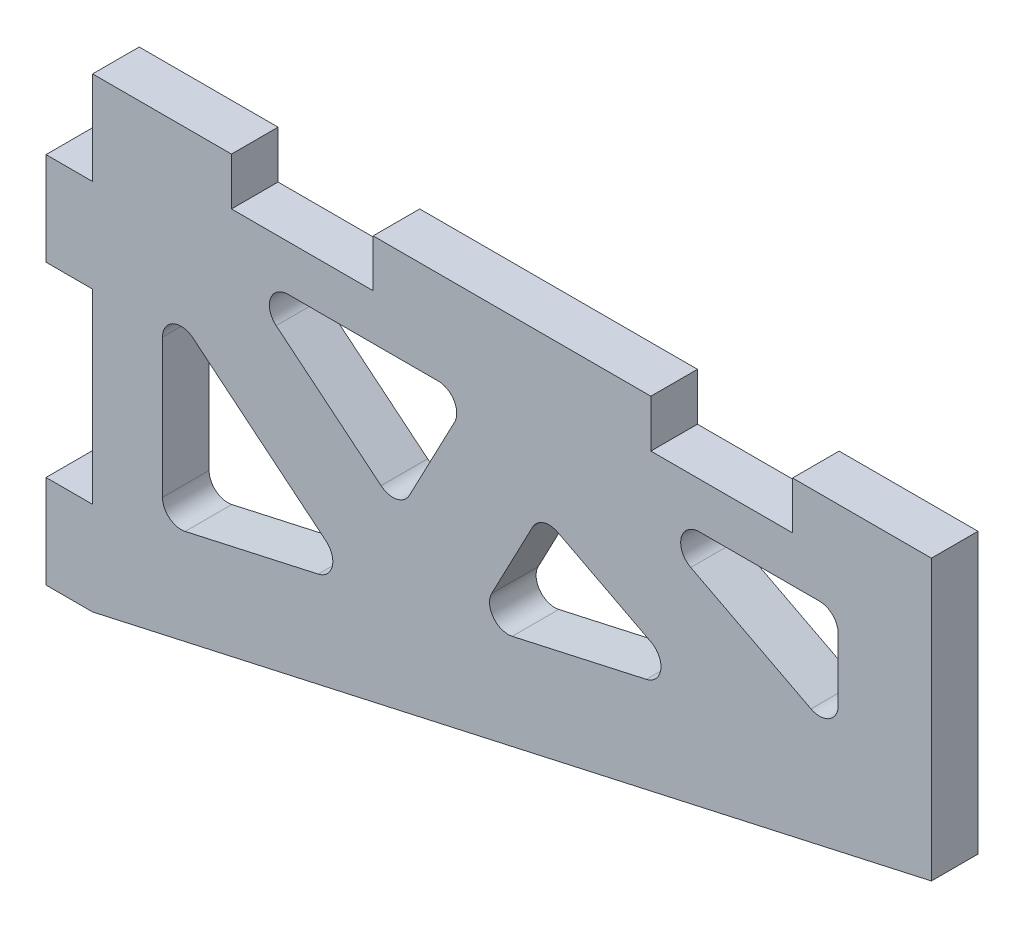
SolidWorks part; units mm, degrees
ref_plane "Front Plane" through (0, 0, 0) normal (0, 0, 1) x (1, 0, 0)
ref_plane "Top Plane" through (0, 0, 0) normal (0, 1, 0) x (1, 0, 0)
ref_plane "Right Plane" through (0, 0, 0) normal (1, 0, 0) x (0, 0, -1)
sketch "Sketch2" plane through (0, 0, 0) normal (0, 0, 1) x (1, 0, 0)
  line L0 (0, -127) -> (27.7435, -127)
  line L5 (0, -69.85) -> (40.1279, -69.85) construction
  line L6 (0, -127) -> (0, -69.85) construction
  line L7 (0, -63.5) -> (45.8652, -63.5) construction
  line L8 (0, -63.5) -> (114.3, -38.1)
  line L9 (114.3, -38.1) -> (114.3, 0)
  line L11 (0, 0) -> (0, -12.7) construction
  line L12 (19.05, 0) -> (19.05, -6.35) construction
  line L13 (0, -63.5) -> (0, -25.4) construction
  line L16 (-6.35, -63.5) -> (0, -63.5)
  line L18 (0, 0) -> (19.05, 0)
  line L20 (-6.35, -12.7) -> (0, -12.7)
  line L21 (0, -25.4) -> (0, -50.8)
  line L22 (0, -50.8) -> (-6.35, -50.8)
  line L23 (-6.35, -50.8) -> (-6.35, -63.5)
  line L24 (0, 0) -> (0, -12.7)
  line L25 (-6.35, -12.7) -> (-6.35, -25.4)
  line L26 (-6.35, -25.4) -> (0, -25.4)
  line L27 (0, -25.4) -> (0, -63.5) construction
  line L28 (0, -12.7) -> (0, 0) construction
  line L29 (-6.35, -63.5) -> (-6.35, 0) construction
  line L30 (19.05, -6.35) -> (38.1, -6.35) construction
  line L31 (38.1, -6.35) -> (38.1, 0) construction
  line L32 (18.923, 0) -> (18.923, -6.477)
  line L33 (18.923, -6.477) -> (38.227, -6.477)
  line L34 (38.227, -6.477) -> (38.227, 0)
  line L35 (57.15, 0) -> (57.15, -20.9685) construction
  line L36 (76.073, -6.477) -> (76.073, 0)
  line L37 (95.377, -6.477) -> (76.073, -6.477)
  line L38 (95.377, 0) -> (95.377, -6.477)
  line L39 (76.2, -6.35) -> (76.2, 0) construction
  line L40 (95.25, -6.35) -> (76.2, -6.35) construction
  line L41 (95.25, 0) -> (95.25, -6.35) construction
  line L42 (38.1, 0) -> (76.2, 0)
  line L43 (95.25, 0) -> (114.3, 0)
  point P21 (-6.35, -31.75)
  dimension "D1" = 57.15
  dimension "D2" = 6.35
  dimension "D3" = 114.3
  dimension "D4" = 12.7
  dimension "D5" = 12.7
  dimension "D6" = 6.35
  dimension "D7" = 38.1
  dimension "D8" = 12.7
  dimension "D9" = 6.35
  dimension "D10" = 19.05
  dimension "D11" = 19.05
  dimension "D13" = 19.05
  dimension "D12" = 0.127
extrude "Boss-Extrude1" add sketch "Sketch2" against normal blind 6.35 contours L22 L23 L16 L8 L9 L18 L20 L21 region at (50.6118, -27.2649, 0)
sketch "Sketch3" plane through (0, 0, 0) normal (0, 0, 1) x (1, 0, 0)
  line L0 (9.525, -12.7) -> (9.525, -48.3735)
  line L1 (9.525, -48.3735) -> (101.6, -27.9124)
  line L2 (101.6, -27.9124) -> (101.6, -12.7)
  line L3 (101.6, -12.7) -> (9.525, -12.7)
  line L4 (0, 0) -> (18.923, 0) construction
  line L5 (114.3, -38.1) -> (114.3, 0) construction
  line L6 (0, -63.5) -> (114.3, -38.1) construction
  line L7 (0, -25.4) -> (0, -50.8) construction
  line L8 (9.525, -12.7) -> (43.7122, -40.7764) construction
  line L9 (13.5551, -7.7928) -> (47.7422, -35.8692)
  line L10 (5.4949, -17.6072) -> (39.6821, -45.6836)
  line L11 (43.7122, -40.7764) -> (58.4566, -12.7) construction
  line L12 (38.0902, -37.824) -> (52.8347, -9.7476)
  line L13 (49.3341, -43.7288) -> (64.0785, -15.6524)
  line L14 (58.4566, -12.7) -> (98.6776, -33.55) construction
  line L17 (61.379, -7.0625) -> (101.6, -27.9124)
  line L18 (55.5342, -18.3375) -> (95.7552, -39.1875)
  arc A0 (13.5551, -7.7928) -> (5.4949, -17.6072) centre (9.525, -12.7) ccw
  arc A1 (39.6821, -45.6836) -> (47.7422, -35.8692) centre (43.7122, -40.7764) ccw
  arc A2 (38.0902, -37.824) -> (49.3341, -43.7288) centre (43.7122, -40.7764) ccw
  arc A3 (64.0785, -15.6524) -> (52.8347, -9.7476) centre (58.4566, -12.7) ccw
  arc A6 (61.379, -7.0625) -> (55.5342, -18.3375) centre (58.4566, -12.7) ccw
  arc A7 (95.7552, -39.1875) -> (101.6, -27.9124) centre (98.6776, -33.55) ccw
  point P4 (26.6186, -26.7382)
  point P18 (51.0844, -26.7382)
  point P27 (78.5671, -23.125)
  dimension "D5" = 6.35
  dimension "D1" = 12.7
  dimension "D2" = 12.7
  dimension "D3" = 12.7
  dimension "D4" = 9.525
extrude "Cut-Extrude1" cut sketch "Sketch3" against normal blind 6.35 contours L10 L0 L1 | L9 L12 L3 | L18 L13 L1 | L3 L17 L2 region at (18.2959, -37.2723, 0) region at (37.5102, -18.7733, 0) region at (65.0863, -30.807, 0) region at (91.8181, -17.7708, 0)
fillet "Fillet1" radius 2.54 12 edges at (82.2848, -32.2047, -3.175) (51.8321, -38.9719, -3.175) (61.1418, -21.2445, -3.175) (101.6, -27.9124, -3.175) (72.2542, -12.7, -3.175) (101.6, -12.7, -3.175) (35.8376, -42.5263, -3.175) (9.525, -20.917, -3.175) (51.2842, -12.7, -3.175) (41.7159, -30.92, -3.175) (19.5304, -12.7, -3.175) (9.525, -48.3735, -3.175)
